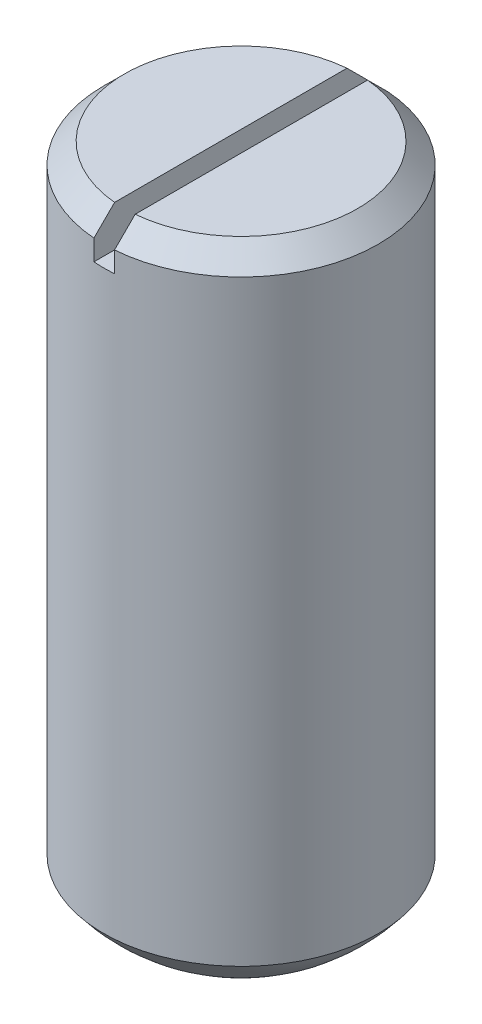
SolidWorks part; units mm, degrees
ref_plane "Face" through (0, 0, 0) normal (0, 0, 1) x (1, 0, 0)
ref_plane "Dessus" through (0, 0, 0) normal (0, 1, 0) x (1, 0, 0)
ref_plane "Droite" through (0, 0, 0) normal (1, 0, 0) x (0, 0, -1)
ref_axis "Axe1" through (0, 0.5, 0) along (0, -1, 0)
sketch "Esquisse1" plane through (0, 0, 0) normal (0, 0, 1) x (1, 0, 0)
  line L0 (0, -10) -> (0, 0) construction
  line L1 (0, 0) -> (1.7, 0)
  line L2 (1.7, 0) -> (2, -0.3)
  line L3 (0, 0) -> (0, 5.1982) construction
  line L5 (2, -0.3) -> (2, -9)
  line L6 (0, -10) -> (0, 0)
  line L7 (-1.5, 0) -> (1.5, 0) construction
  arc A0 (2, -9) -> (0, -10) centre (0, -7.5) cw
  dimension "D2" = 45
  dimension "D4" = 2.5
  dimension "D1" = 2
  dimension "Diamètre nominal" = 3
  dimension "D3" = 0.3
  dimension "Longueur" = 10
revolve "Tige" add sketch "Esquisse1" angle 360 about L3
sketch "Esquisse2" plane through (0, 0, 0) normal (0, 1, 0) x (1, 0, 0)
  line L0 (0, -2) -> (0, 2) construction
  line L1 (5, 0) -> (-5, 0) construction
  line L2 (0.15, -2) -> (-0.15, -2)
  line L3 (0.15, -2) -> (0.15, 2)
  line L4 (0.15, 2) -> (-0.15, 2)
  line L5 (-0.15, -2) -> (-0.15, 2)
  circle A1 centre (0, 0) radius 2 construction
  dimension "D1" = 0.3
extrude "Fente" cut sketch "Esquisse2" against normal blind 0.6
sketch "Esquisse3" plane through (0, 0, 0) normal (0, 1, 0) x (-1, 0, 0)
  circle A0 centre (0, 0) radius 2
  arc A1 (-0.15, 1.9944) -> (-0.15, -1.9944) centre (0, 0) ccw construction
equation "\"D3@Esquisse1\" = \"Diamètre nominal@Esquisse1\"*0.1"
equation "\"D1@Esquisse2\" = \"Diamètre nominal@Esquisse1\"/10"
equation "\"D1@Fente\" = \"Diamètre nominal@Esquisse1\"*0.2"
equation "\"D4@Esquisse1\" = \"Diamètre nominal@Esquisse1\"/1.2"
